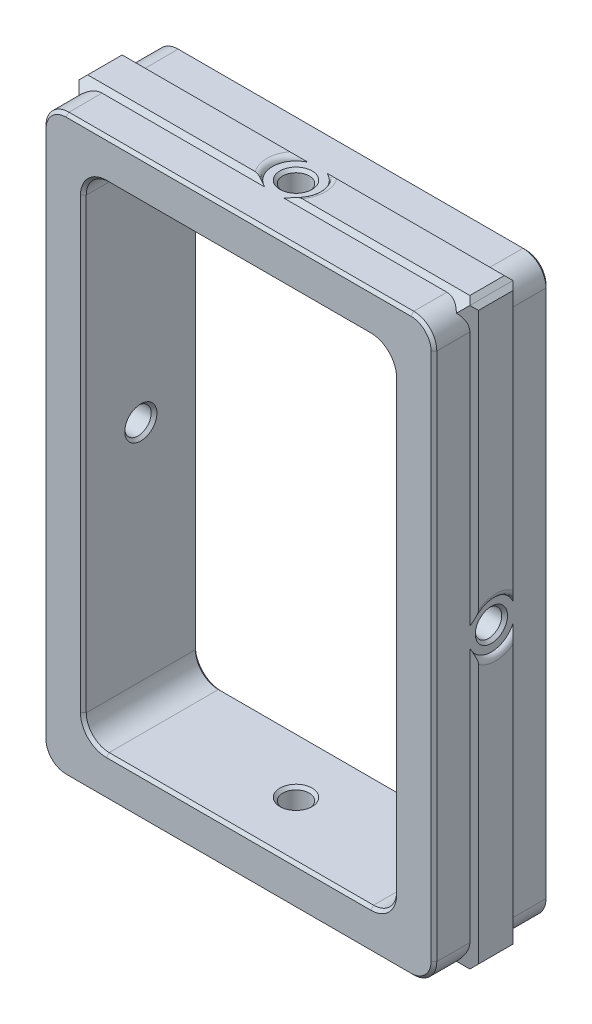
SolidWorks part; units mm, degrees
ref_plane "Front" through (0, 0, 0) normal (0, 0, 1) x (1, 0, 0)
ref_plane "Top" through (0, 0, 0) normal (0, 1, 0) x (1, 0, 0)
ref_plane "Right" through (0, 0, 0) normal (1, 0, 0) x (0, 0, -1)
sketch "Skizze1" plane through (0, 0, 0) normal (0, 0, 1) x (1, 0, 0)
  line L0 (34, 93) -> (34, 7) construction
  line L1 (0, 0) -> (68, 0)
  line L2 (0, 0) -> (0, 100)
  line L3 (0, 100) -> (68, 100)
  line L4 (68, 0) -> (68, 100)
  line L5 (11.1328, 7) -> (56.8672, 7)
  line L6 (7, 13.5818) -> (7, 86.4182)
  line L7 (11.1328, 93) -> (56.8672, 93)
  line L8 (61, 13.5818) -> (61, 86.4182)
  line L18 (7, 86.4182) -> (7, 93)
  line L19 (7, 93) -> (11.1328, 93)
  line L20 (56.8672, 93) -> (61, 93)
  line L21 (61, 93) -> (61, 86.4182)
  line L22 (61, 13.5818) -> (61, 7)
  line L23 (61, 7) -> (56.8672, 7)
  line L24 (11.1328, 7) -> (7, 7)
  line L25 (7, 7) -> (7, 13.5818)
  dimension "D1" = 7
  dimension "D2" = 7
  dimension "D3" = 7
  dimension "D4" = 7
extrude "Aufsatz-Linear austragen1" add sketch "Skizze1" along normal blind 20 contours L1 L4 L3 L2 L24 L25 L6 L18 L19 L7 L20 L21 L8 L22 L23 L5 region at (1.2093, 50, 0)
sketch "Skizze2" plane through (0, 0, 0) normal (0, 0, 1) x (1, 0, 0)
  line L1 (0, 100) -> (68, 100)
  line L2 (0, 100) -> (0, 0)
  line L3 (0, 0) -> (68, 0)
  line L4 (68, 100) -> (68, 0)
extrude "Aufsatz-Linear austragen2" [suppressed] add sketch "Skizze2" along normal blind 0.6
sketch "Skizze3" plane through (0, 0, 0) normal (0, -1, 0) x (1, 0, 0)
  line L0 (0, 10) -> (-11.2685, 10) construction
  line L1 (0, 20) -> (0, 0) construction
  line L2 (34, 0) -> (34, 20) construction
  line L5 (0, 13.75) -> (-0.75, 13)
  line L6 (-0.75, 13) -> (-0.75, 7)
  line L7 (0, 13.75) -> (0, 6.25)
  line L8 (0, 6.25) -> (-0.75, 7)
  line L9 (68, 13.75) -> (68.75, 13)
  line L10 (68.75, 13) -> (68.75, 7)
  line L11 (68, 6.25) -> (68.75, 7)
  line L12 (68, 13.75) -> (68, 6.25)
  line L13 (0, 20) -> (68, 20) construction
  line L14 (0, 0) -> (68, 0) construction
  point P15 (-0.75, 10)
  dimension "D1" = 45
  dimension "D2" = 7.5
  dimension "D3" = 0.75
extrude "Aufsatz-Linear austragen3" add sketch "Skizze3" against normal up to surface (100 mm away) up to face at (34, 100, 10)
sketch "Skizze4" plane through (0, 0, 0) normal (-1, 0, 0) x (0, 0, 1)
  line L0 (10, 100) -> (10, 106.8008) construction
  line L1 (7, 100) -> (13, 100) construction
  line L2 (13.75, 100) -> (13, 100.75)
  line L3 (13, 100.75) -> (7, 100.75)
  line L4 (13.75, 100) -> (6.25, 100)
  line L5 (6.25, 100) -> (7, 100.75)
  line L6 (0, 50) -> (20, 50) construction
  line L8 (13.75, 0) -> (13, -0.75)
  line L9 (13, -0.75) -> (7, -0.75)
  line L10 (6.25, 0) -> (7, -0.75)
  line L11 (13.75, 0) -> (6.25, 0)
  line L12 (0, 0) -> (0, 100) construction
  point P10 (10, 100.75)
  dimension "D1" = 0.75
  dimension "D2" = 45
extrude "Aufsatz-Linear austragen4" add sketch "Skizze4" against normal up to surface (68 mm away) up to face at (68, 50, 3.125)
sketch "Skizze5" plane through (0, 93, 0) normal (0, -1, 0) x (1, 0, 0)
  line L0 (34, 0) -> (34, 20) construction
  line L3 (0, 20) -> (68, 20) construction
  line L4 (0, 0) -> (68, 0) construction
  circle A0 centre (34, 10) radius 2.3
  dimension "D1" = 4.6
extrude "Schnitt-Linear austragen1" cut sketch "Skizze5" against normal blind 20
ref_plane "Ebene1" through (0, 50, 0) normal (0, 1, 0) x (1, 0, 0)
ref_plane "Ebene2" through (34, 0, 0) normal (-1, 0, 0) x (0, 0, 1)
sketch "Skizze6" plane through (7, 0, 0) normal (1, 0, 0) x (0, 0, -1)
  line L0 (-20, 50) -> (0, 50) construction
  line L3 (-20, 0) -> (-20, 100) construction
  line L4 (0, 0) -> (0, 100) construction
  circle A0 centre (-10, 50) radius 2.3
  dimension "D1" = 4.6
extrude "Schnitt-Linear austragen2" cut sketch "Skizze6" against normal blind 20
sketch "Skizze7" plane through (0, 100, 0) normal (0, 1, 0) x (1, 0, 0)
  circle A0 centre (34, -10) radius 4.1
  dimension "D1" = 8.2
extrude "Schnitt-Linear austragen3" cut sketch "Skizze7" along normal blind 20
sketch "Skizze8" plane through (0, 0, 0) normal (-1, 0, 0) x (0, 0, 1)
  line L1 (10, 52.3) -> (10, 47.7) construction
  circle A0 centre (10, 50) radius 4.1
  circle A1 centre (10, 50) radius 2.3 construction
  dimension "D1" = 8.2
extrude "Schnitt-Linear austragen4" cut sketch "Skizze8" along normal blind 20
mirror "Spiegeln1" about plane through (0, 50, 0) normal (0, 1, 0) of "Schnitt-Linear austragen3", "Schnitt-Linear austragen1"
mirror "Spiegeln2" about plane through (34, 0, 0) normal (-1, 0, 0) of "Schnitt-Linear austragen4", "Schnitt-Linear austragen2"
fillet "Verrundung1" radius 1 8 edges at (-0.75, 54.1, 10) (-0.75, 45.9, 10) (38.1, 100.75, 10) (29.9, 100.75, 10) (68.75, 54.1, 10) (68.75, 45.9, 10) (38.1, -0.75, 10) (29.9, -0.75, 10)
chamfer "Fase1" distance 0.75 angle 45 8 edges at (68.75, 100, 10) (68, 100.75, 10) (-0.75, 100, 10) (0, 100.75, 10) (0, -0.75, 10) (-0.75, 0, 10) (68.75, 0, 10) (68, -0.75, 10)
fillet "Verrundung2" radius 4 8 edges at (68, 0, 3.125) (68, 0, 16.875) (68, 100, 16.875) (68, 100, 3.125) (0, 100, 3.125) (0, 100, 16.875) (0, 0, 3.125) (0, 0, 16.875)
chamfer "Fase2" [suppressed] distance 0.5 angle 45
fillet "Fillet1" radius 4 4 edges at (7, 7, 10) (61, 7, 10) (61, 93, 10) (7, 93, 10)
chamfer "Chamfer1" distance 0.5 angle 45 40 edges at (61, 50, 20) (34, 93, 20) (7, 50, 20) (34, 7, 20) (66.8284, 1.1716, 20) (34, 0, 20) (1.1716, 1.1716, 20) (0, 50, 20) (1.1716, 98.8284, 20) (34, 100, 20) (66.8284, 98.8284, 20) (68, 50, 20) (7, 50, 0) (34, 93, 0) (61, 50, 0) (34, 7, 0) (1.1716, 98.8284, 0) (0, 50, 0) (1.1716, 1.1716, 0) (34, 0, 0) (66.8284, 1.1716, 0) (68, 50, 0) (66.8284, 98.8284, 0) (34, 100, 0) (59.8284, 91.8284, 20) (8.1716, 91.8284, 20) (8.1716, 8.1716, 20) (59.8284, 8.1716, 20) (8.1716, 8.1716, 0) (8.1716, 91.8284, 0) (59.8284, 91.8284, 0) (59.8284, 8.1716, 0) (34, 0, 7.7) (34, 7, 7.7) (68, 50, 7.7) (61, 52.3, 10) (34, 100, 12.3) (34, 93, 7.7) (0, 50, 12.3) (7, 52.3, 10)
